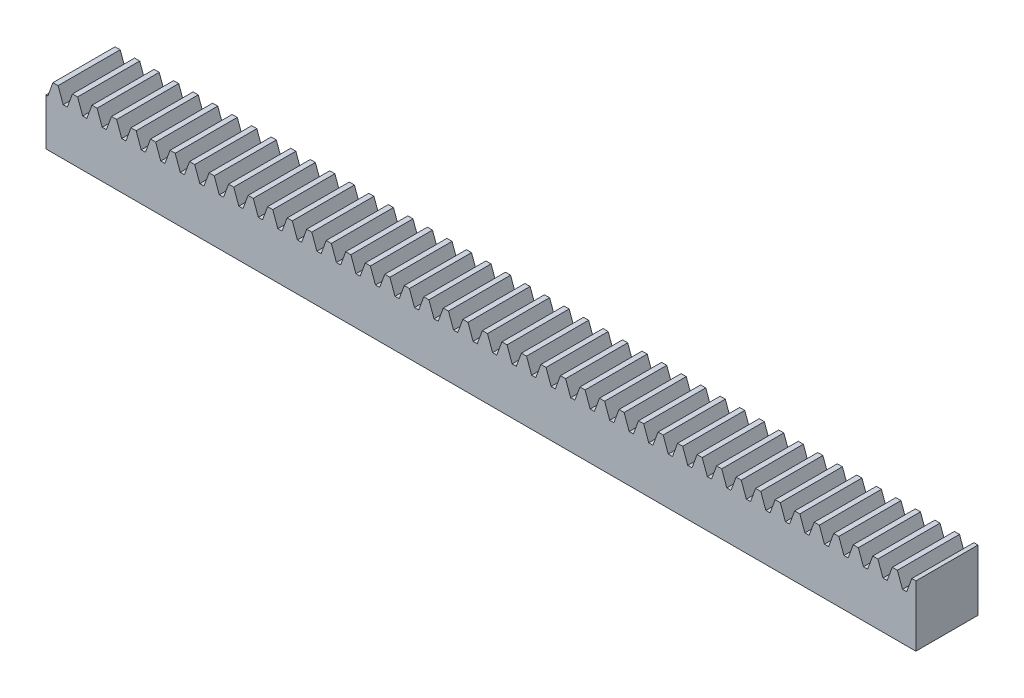
SolidWorks part; units mm, degrees
ref_plane "Front" through (0, 0, 0) normal (0, 0, 1) x (1, 0, 0)
ref_plane "Top" through (0, 0, 0) normal (0, 1, 0) x (1, 0, 0)
ref_plane "Right" through (0, 0, 0) normal (1, 0, 0) x (0, 0, -1)
sketch "Ritning 1" plane through (0, 0, 0) normal (0, 0, 1) x (1, 0, 0)
  line L1 (-124.1, -4.9) -> (125.9, -4.9)
  line L2 (-124.1, -4.9) -> (-124.1, 4.9)
  line L3 (-124.1, 4.9) -> (125.9, 4.9)
  line L4 (125.9, -4.9) -> (125.9, 4.9)
  dimension "D1" = 125.9
  dimension "D2" = 124.1
  dimension "D3" = 4.9
  dimension "D4" = 4.9
extrude "Kuggstångsämne" add sketch "Ritning 1" along normal blind 10
sketch "Ritning 2" plane through (0, 0, 10) normal (0, 0, 1) x (1, 0, 0)
  line L0 (-124.4383, 2.65) -> (-123.7617, 2.65)
  line L1 (-125.2572, 4.9) -> (-124.1, 6.0572)
  line L2 (125.9, -4.9) -> (125.9, 4.9) construction
  line L3 (-124.1, -4.9) -> (125.9, -4.9) construction
  line L7 (-124.1, 6.0572) -> (-122.9428, 4.9)
  line L9 (-122.9428, 4.9) -> (-123.7617, 2.65)
  spline S0 degree 3 poles (-125.2572, 4.9) (-124.9842, 4.15) (-124.7113, 3.4) (-124.4383, 2.65) knots 0 0 0 0 1 1 1 1
  dimension "D1" = 248.8428
  dimension "D2" = 249.6617
  dimension "D3" = 250
  dimension "D4" = 250.3383
  dimension "D5" = 7.55
  dimension "D6" = 9.8
extrude "Kugglucka" cut sketch "Ritning 2" against normal blind 10
ref_axis "Axis" through (125.9, 4.9, 10) along (-1, 0, 0)
pattern_linear "LPattern" count 80 spacing 3.1416 along (1, 0, 0) of "Kugglucka"
sketch "Sketch1" plane through (0, 0, 10) normal (0, 0, 1) x (1, 0, 0)
  line L2 (-124.1, -4.9) -> (125.9, -4.9) construction
  line L3 (-14.1, -4.9) -> (-14.1, 28.8426)
  line L4 (-14.1, 28.8426) -> (-144.1559, 20.3118)
  line L5 (-144.1559, 20.3118) -> (-144.1559, -37.129)
  line L7 (-144.1559, -37.129) -> (-16.7625, -41.11)
  line L8 (-16.7625, -41.11) -> (-14.1, -4.9)
extrude "Cut-Extrude1" cut sketch "Sketch1" against normal blind 10
